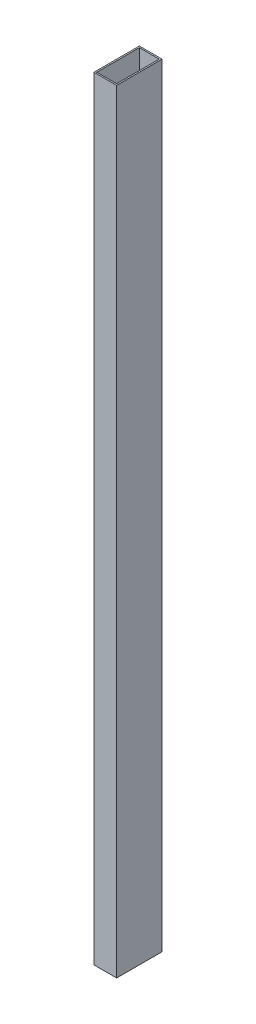
SolidWorks part; units mm, degrees
material "6061-T6 (SS)"
ref_plane "Front" through (0, 0, 0) normal (0, 0, 1) x (1, 0, 0)
ref_plane "Top" through (0, 0, 0) normal (0, 1, 0) x (1, 0, 0)
ref_plane "Right" through (0, 0, 0) normal (1, 0, 0) x (0, 0, -1)
sketch "Sketch1" plane through (0, 0, 0) normal (0, 1, 0) x (1, 0, 0)
  line L1 (12.7, 25.4) -> (-12.7, 25.4)
  line L2 (12.7, 25.4) -> (12.7, -25.4)
  line L3 (12.7, -25.4) -> (-12.7, -25.4)
  line L4 (-12.7, 25.4) -> (-12.7, -25.4)
  line L5 (12.7, 25.4) -> (-12.7, -25.4) construction
  line L6 (12.7, -25.4) -> (-12.7, 25.4) construction
  point P0 (0, 0)
  dimension "D1" = 25.4
  dimension "D2" = 50.8
extrude "Extrude-Thin1" add sketch "Sketch1" along normal blind 863.6 thin thin type one direction reverse wall 1.5875
